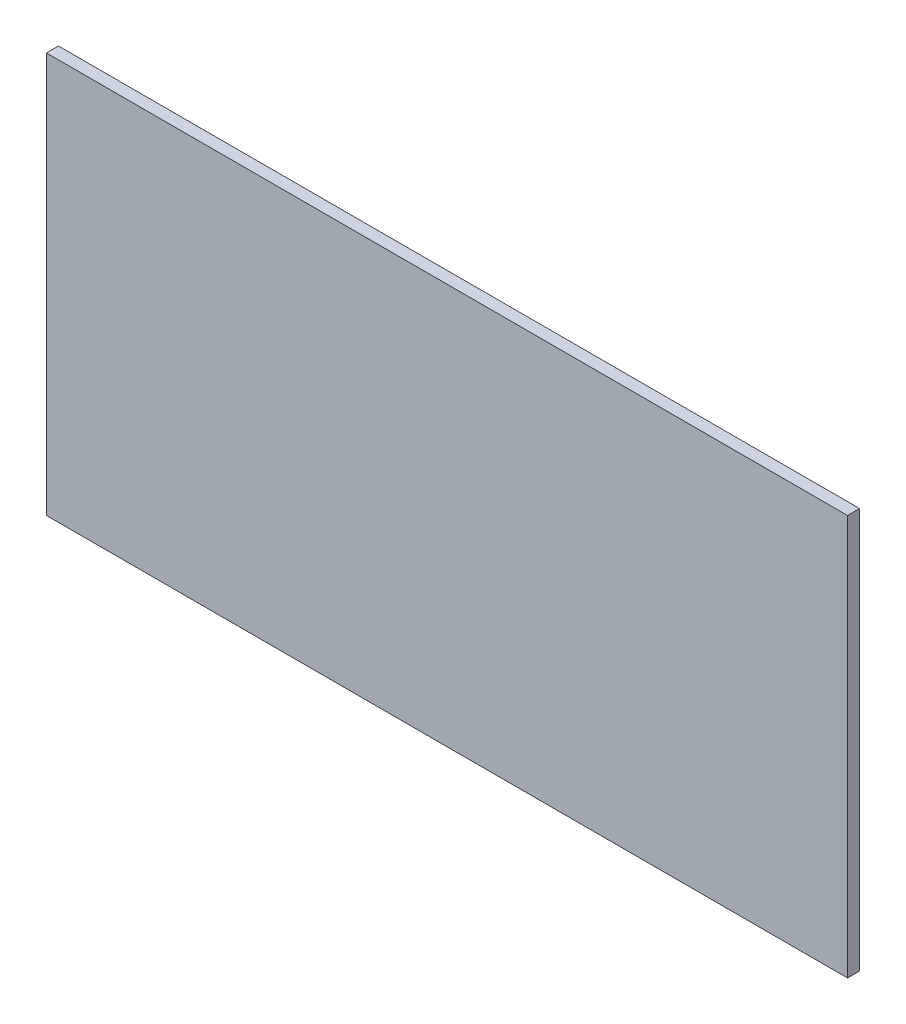
SolidWorks part; units mm, degrees
ref_plane "Спереди" through (0, 0, 0) normal (0, 0, 1) x (1, 0, 0)
ref_plane "Сверху" through (0, 0, 0) normal (0, 1, 0) x (1, 0, 0)
ref_plane "Справа" through (0, 0, 0) normal (1, 0, 0) x (0, 0, -1)
sketch "Эскиз1" plane through (0, 0, 0) normal (0, 0, 1) x (1, 0, 0)
  line L1 (-100, -50) -> (100, -50)
  line L2 (-100, -50) -> (-100, 50)
  line L3 (-100, 50) -> (100, 50)
  line L4 (100, -50) -> (100, 50)
  line L5 (-100, -50) -> (100, 50) construction
  line L6 (-100, 50) -> (100, -50) construction
  point P0 (0, 0)
extrude "abot_base" add sketch "Эскиз1" along normal blind 3
ref_plane "Плоскость2" through (40, 0, 0) normal (1, 0, 0) x (0, 0, -1)
ref_axis "Ось2" through (40, -50, 3) along (0, 1, 0)
ref_plane "Плоскость3" through (0, 0, 0) normal (0, -1, 0) x (-1, 0, 0)
ref_axis "Ось3" through (-100, 0, 3) along (1, 0, 0)
ref_point "up_center"
